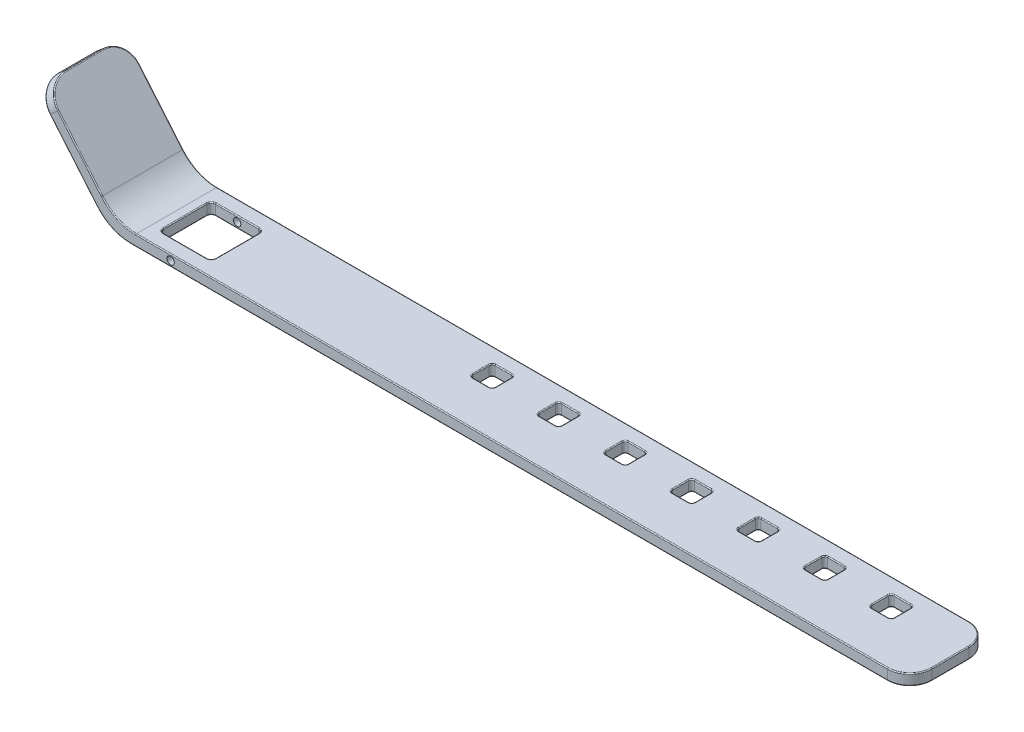
SolidWorks part; units mm, degrees
ref_plane "Front Plane" through (0, 0, 0) normal (0, 0, 1) x (1, 0, 0)
ref_plane "Top Plane" through (0, 0, 0) normal (0, 1, 0) x (1, 0, 0)
ref_plane "Right Plane" through (0, 0, 0) normal (1, 0, 0) x (0, 0, -1)
sketch "Sketch2" plane through (0, 0, 0) normal (0, 0, 1) x (1, 0, 0)
  line L0 (-98.5968, 5.7865) -> (-114.2836, 24.4813)
  line L1 (-89.4043, 1.5) -> (120, 1.5)
  line L3 (-90.8032, -1.5) -> (120, -1.5)
  line L4 (120, 1.5) -> (120, -1.5)
  line L5 (-114.2836, 24.4813) -> (-116.5818, 22.553)
  line L6 (-116.5818, 22.553) -> (-99.9958, 2.7865)
  circle A0 centre (-80, 0) radius 1
  arc A1 (-89.4043, 1.5) -> (-98.5968, 5.7865) centre (-89.4043, 13.5) cw
  arc A2 (-90.8032, -1.5) -> (-99.9958, 2.7865) centre (-90.8032, 10.5) cw
  point P4 (-80, 0)
  point P12 (-95, 1.5)
  dimension "D7" = 2
  dimension "D2" = 12
  dimension "D12" = 12
  dimension "D1" = 215
  dimension "D5" = 1.5
  dimension "D6" = 200
  dimension "D8" = 130
  dimension "D9" = 30
  dimension "D10" = 3
  dimension "D11" = 90
extrude "Boss-Extrude1" add sketch "Sketch2" along normal blind 11 and the other way blind 11
fillet "Fillet1" radius 6 4 edges at (120, 0, 11) (120, 0, -11) (-115.4327, 23.5172, -11) (-115.4327, 23.5172, 11)
sketch "Sketch4" plane through (0, 1.5, 0) normal (0, 1, 0) x (1, 0, 0)
  line L0 (114, -11) -> (-89.4043, -11) construction
  line L1 (-85.8, 7) -> (-74.2, 7)
  line L2 (-87, 5.8) -> (-87, -5.8)
  line L3 (-85.8, -7) -> (-74.2, -7)
  line L4 (-73, 5.8) -> (-73, -5.8)
  line L5 (114, 11) -> (-89.4043, 11) construction
  line L34 (97.8, 7) -> (102.2, 7)
  line L35 (120, 5) -> (120, -5) construction
  line L36 (-114.2836, 5) -> (-114.2836, -5) construction
  line L65 (-73, 0) -> (-114.2836, 0) construction
  line L66 (97, 6.2) -> (97, 1.8)
  line L67 (97.8, 1) -> (102.2, 1)
  line L68 (103, 6.2) -> (103, 1.8)
  line L69 (79, 6.2) -> (79, 1.8)
  line L70 (79.8, 7) -> (84.2, 7)
  line L71 (85, 6.2) -> (85, 1.8)
  line L72 (79.8, 1) -> (84.2, 1)
  line L73 (61, 6.2) -> (61, 1.8)
  line L74 (61.8, 7) -> (66.2, 7)
  line L75 (67, 6.2) -> (67, 1.8)
  line L76 (61.8, 1) -> (66.2, 1)
  line L77 (43, 6.2) -> (43, 1.8)
  line L78 (43.8, 7) -> (48.2, 7)
  line L79 (49, 6.2) -> (49, 1.8)
  line L80 (43.8, 1) -> (48.2, 1)
  line L81 (25, 6.2) -> (25, 1.8)
  line L82 (25.8, 7) -> (30.2, 7)
  line L83 (31, 6.2) -> (31, 1.8)
  line L84 (25.8, 1) -> (30.2, 1)
  line L85 (7, 6.2) -> (7, 1.8)
  line L86 (7.8, 7) -> (12.2, 7)
  line L87 (13, 6.2) -> (13, 1.8)
  line L88 (7.8, 1) -> (12.2, 1)
  line L89 (-11, 6.2) -> (-11, 1.8)
  line L90 (-10.2, 7) -> (-5.8, 7)
  line L91 (-5, 6.2) -> (-5, 1.8)
  line L92 (-10.2, 1) -> (-5.8, 1)
  arc A0 (-85.8, -7) -> (-87, -5.8) centre (-85.8, -5.8) cw
  arc A1 (-74.2, -7) -> (-73, -5.8) centre (-74.2, -5.8) ccw
  arc A2 (-73, 5.8) -> (-74.2, 7) centre (-74.2, 5.8) ccw
  arc A3 (-85.8, 7) -> (-87, 5.8) centre (-85.8, 5.8) ccw
  arc A58 (97.8, 1) -> (97, 1.8) centre (97.8, 1.8) cw
  arc A59 (103, 1.8) -> (102.2, 1) centre (102.2, 1.8) cw
  arc A60 (103, 6.2) -> (102.2, 7) centre (102.2, 6.2) ccw
  arc A61 (97.8, 7) -> (97, 6.2) centre (97.8, 6.2) ccw
  arc A62 (79.8, 7) -> (79, 6.2) centre (79.8, 6.2) ccw
  arc A63 (79.8, 1) -> (79, 1.8) centre (79.8, 1.8) cw
  arc A64 (85, 6.2) -> (84.2, 7) centre (84.2, 6.2) ccw
  arc A65 (85, 1.8) -> (84.2, 1) centre (84.2, 1.8) cw
  arc A66 (61.8, 7) -> (61, 6.2) centre (61.8, 6.2) ccw
  arc A67 (61.8, 1) -> (61, 1.8) centre (61.8, 1.8) cw
  arc A68 (67, 6.2) -> (66.2, 7) centre (66.2, 6.2) ccw
  arc A69 (67, 1.8) -> (66.2, 1) centre (66.2, 1.8) cw
  arc A70 (43.8, 7) -> (43, 6.2) centre (43.8, 6.2) ccw
  arc A71 (43.8, 1) -> (43, 1.8) centre (43.8, 1.8) cw
  arc A72 (49, 6.2) -> (48.2, 7) centre (48.2, 6.2) ccw
  arc A73 (49, 1.8) -> (48.2, 1) centre (48.2, 1.8) cw
  arc A74 (25.8, 7) -> (25, 6.2) centre (25.8, 6.2) ccw
  arc A75 (25.8, 1) -> (25, 1.8) centre (25.8, 1.8) cw
  arc A76 (31, 6.2) -> (30.2, 7) centre (30.2, 6.2) ccw
  arc A77 (31, 1.8) -> (30.2, 1) centre (30.2, 1.8) cw
  arc A78 (7.8, 7) -> (7, 6.2) centre (7.8, 6.2) ccw
  arc A79 (7.8, 1) -> (7, 1.8) centre (7.8, 1.8) cw
  arc A80 (13, 6.2) -> (12.2, 7) centre (12.2, 6.2) ccw
  arc A81 (13, 1.8) -> (12.2, 1) centre (12.2, 1.8) cw
  arc A82 (-10.2, 7) -> (-11, 6.2) centre (-10.2, 6.2) ccw
  arc A83 (-10.2, 1) -> (-11, 1.8) centre (-10.2, 1.8) cw
  arc A84 (-5, 6.2) -> (-5.8, 7) centre (-5.8, 6.2) ccw
  arc A85 (-5, 1.8) -> (-5.8, 1) centre (-5.8, 1.8) cw
  point P12 (-73, -7)
  point P15 (-73, 7)
  point P18 (-87, 7)
  point P29 (97, 1)
  point P32 (103, 1)
  point P39 (97, 7)
  dimension "D5" = 1.2
  dimension "D10" = 0.8
  dimension "D1" = 14
  dimension "D2" = 14
  dimension "D3" = 4
  dimension "D4" = 6
  dimension "D6" = 6
  dimension "D7" = 17
  dimension "D8" = 193
  dimension "D9" = 4
  dimension "D11" = 7
extrude "Cut-Extrude2" cut sketch "Sketch4" against normal up to next
fillet "Fillet3" radius 0.25 152 edges at (-95.8747, -0.3757, -11) (-106.3604, 10.3716, -11) (-115.4522, 21.2068, -9.2426) (-116.5818, 22.553, 0) (-115.4522, 21.2068, 9.2426) (-106.3604, 10.3716, 11) (-95.8747, -0.3757, 11) (-94.4757, 2.6243, -11) (-104.5119, 12.8358, -11) (-113.154, 23.1351, -9.2426) (-114.2836, 24.4813, 0) (-113.154, 23.1351, 9.2426) (-104.5119, 12.8358, 11) (-94.4757, 2.6243, 11) (-86.6485, -1.5, -6.6485) (-80, -1.5, -7) (-73.3515, -1.5, -6.6485) (-73, -1.5, 0) (-73.3515, -1.5, 6.6485) (-80, -1.5, 7) (-86.6485, -1.5, 6.6485) (-87, -1.5, 0) (118.2426, -1.5, -9.2426) (11.5984, -1.5, -11) (11.5984, -1.5, 11) (118.2426, -1.5, 9.2426) (120, -1.5, 0) (-11, -1.5, -4) (-10.7657, -1.5, -6.7657) (-8, -1.5, -7) (-5.2343, -1.5, -6.7657) (-5, -1.5, -4) (-5.2343, -1.5, -1.2343) (-8, -1.5, -1) (-10.7657, -1.5, -1.2343) (7, -1.5, -4) (7.2343, -1.5, -6.7657) (10, -1.5, -7) (12.7657, -1.5, -6.7657) (13, -1.5, -4) (12.7657, -1.5, -1.2343) (10, -1.5, -1) (7.2343, -1.5, -1.2343) (25, -1.5, -4) (25.2343, -1.5, -6.7657) (28, -1.5, -7) (30.7657, -1.5, -6.7657) (31, -1.5, -4) (30.7657, -1.5, -1.2343) (28, -1.5, -1) (25.2343, -1.5, -1.2343) (43, -1.5, -4) (43.2343, -1.5, -6.7657) (46, -1.5, -7) (48.7657, -1.5, -6.7657) (49, -1.5, -4) (48.7657, -1.5, -1.2343) (46, -1.5, -1) (43.2343, -1.5, -1.2343) (61, -1.5, -4) (61.2343, -1.5, -6.7657) (64, -1.5, -7) (66.7657, -1.5, -6.7657) (67, -1.5, -4) (66.7657, -1.5, -1.2343) (64, -1.5, -1) (61.2343, -1.5, -1.2343) (79, -1.5, -4) (79.2343, -1.5, -6.7657) (82, -1.5, -7) (84.7657, -1.5, -6.7657) (85, -1.5, -4) (84.7657, -1.5, -1.2343) (82, -1.5, -1) (79.2343, -1.5, -1.2343) (97, -1.5, -4) (97.2343, -1.5, -6.7657) (100, -1.5, -7) (102.7657, -1.5, -6.7657) (103, -1.5, -4) (102.7657, -1.5, -1.2343) (100, -1.5, -1) (97.2343, -1.5, -1.2343) (12.2978, 1.5, -11) (118.2426, 1.5, -9.2426) (120, 1.5, 0) (118.2426, 1.5, 9.2426) (12.2978, 1.5, 11) (-8, 1.5, -1) (-5.2343, 1.5, -1.2343) (-5, 1.5, -4) (-5.2343, 1.5, -6.7657) (-8, 1.5, -7) (-10.7657, 1.5, -6.7657) (-11, 1.5, -4) (-10.7657, 1.5, -1.2343) (10, 1.5, -1) (12.7657, 1.5, -1.2343) (13, 1.5, -4) (12.7657, 1.5, -6.7657) (10, 1.5, -7) (7.2343, 1.5, -6.7657) (7, 1.5, -4) (7.2343, 1.5, -1.2343) (28, 1.5, -1) (30.7657, 1.5, -1.2343) (31, 1.5, -4) (30.7657, 1.5, -6.7657) (28, 1.5, -7) (25.2343, 1.5, -6.7657) (25, 1.5, -4) (25.2343, 1.5, -1.2343) (46, 1.5, -1) (48.7657, 1.5, -1.2343) (49, 1.5, -4) (48.7657, 1.5, -6.7657) (46, 1.5, -7) (43.2343, 1.5, -6.7657) (43, 1.5, -4) (43.2343, 1.5, -1.2343) (64, 1.5, -1) (66.7657, 1.5, -1.2343) (67, 1.5, -4) (66.7657, 1.5, -6.7657) (64, 1.5, -7) (61.2343, 1.5, -6.7657) (61, 1.5, -4) (61.2343, 1.5, -1.2343) (82, 1.5, -1) (84.7657, 1.5, -1.2343) (85, 1.5, -4) (84.7657, 1.5, -6.7657) (82, 1.5, -7) (79.2343, 1.5, -6.7657) (79, 1.5, -4) (79.2343, 1.5, -1.2343) (100, 1.5, -1) (102.7657, 1.5, -1.2343) (103, 1.5, -4) (102.7657, 1.5, -6.7657) (100, 1.5, -7) (97.2343, 1.5, -6.7657) (97, 1.5, -4) (97.2343, 1.5, -1.2343) (-80, 1.5, 7) (-73.3515, 1.5, 6.6485) (-73, 1.5, 0) (-73.3515, 1.5, -6.6485) (-80, 1.5, -7) (-86.6485, 1.5, -6.6485) (-87, 1.5, 0) (-86.6485, 1.5, 6.6485)
